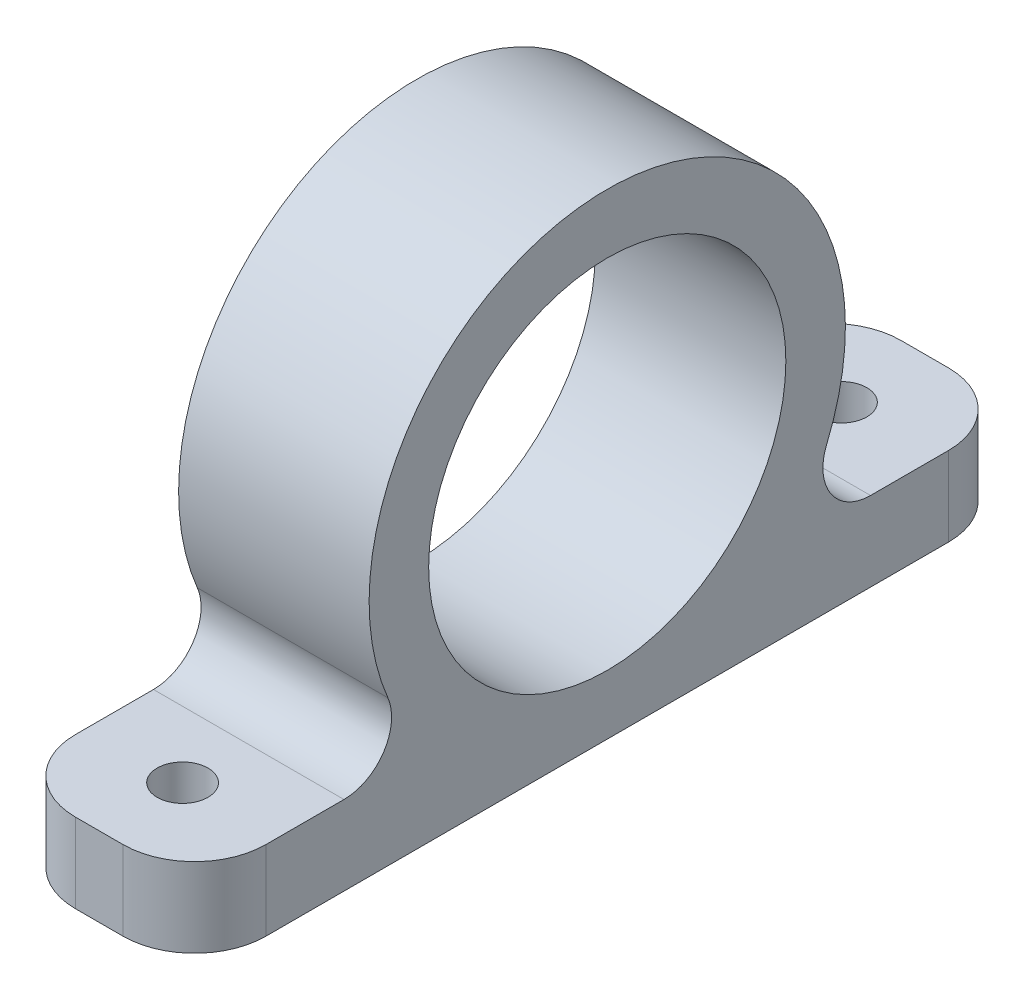
SolidWorks part; units mm, degrees
ref_plane "Alzado" through (0, 0, 0) normal (0, 0, 1) x (1, 0, 0)
ref_plane "Planta" through (0, 0, 0) normal (0, 1, 0) x (1, 0, 0)
ref_plane "Vista lateral" through (0, 0, 0) normal (1, 0, 0) x (0, 0, -1)
sketch "Croquis1" plane through (0, 0, 0) normal (1, 0, 0) x (0, 0, -1)
  line L0 (-26, -15) -> (26, -15)
  line L1 (0, 0) -> (0, -15) construction
  line L2 (-26, -15) -> (-26, -10)
  line L3 (26, -15) -> (26, -10)
  line L4 (-26, -10) -> (-11.1803, -10)
  line L5 (26, -10) -> (11.1803, -10)
  arc A0 (11.1803, -10) -> (-11.1803, -10) centre (0, 0) ccw
  point P7 (0, -15)
  dimension "D1" = 30
  dimension "D2" = 52
  dimension "D3" = 5
  dimension "D4" = 5
  dimension "D5" = 15
extrude "Saliente-Extruir1" add sketch "Croquis1" along normal blind 12
sketch "Croquis2" plane through (0, 0, 0) normal (-1, 0, 0) x (0, 0, 1)
  circle A0 centre (0, 0) radius 11.25
  dimension "D1" = 22.5
extrude "Cortar-Extruir1" cut sketch "Croquis2" against normal through all
fillet "Redondeo1" radius 3 2 edges at (6, -10, 11.1803) (6, -10, -11.1803)
fillet "Redondeo2" radius 4.5 4 edges at (12, -12.5, -26) (0, -12.5, -26) (0, -12.5, 26) (12, -12.5, 26)
sketch "Croquis3" plane through (0, -10, 0) normal (0, 1, 0) x (1, 0, 0)
  line L0 (-1000, 0) -> (49000, 0) construction
  circle A0 centre (6, 20.75) radius 1.6
  circle A1 centre (6, -20.75) radius 1.6
  dimension "D1" = 3.2
  dimension "D2" = 6
  dimension "D3" = 20.75
extrude "Cortar-Extruir2" cut sketch "Croquis3" against normal through all and the other way blind 10
